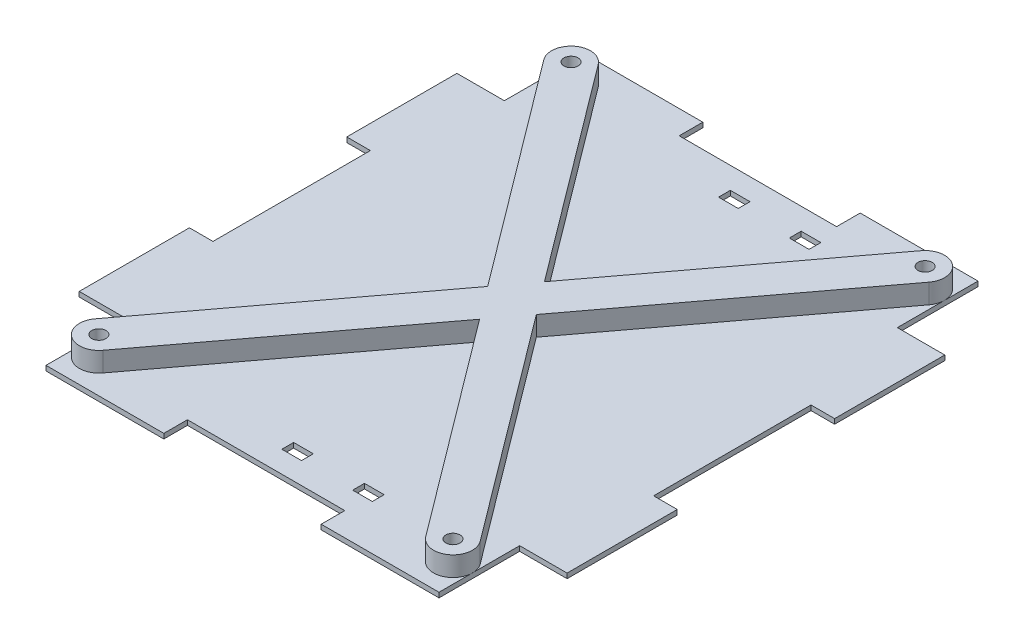
SolidWorks part; units mm, degrees
ref_plane "Front Plane" through (0, 0, 0) normal (0, 0, 1) x (1, 0, 0)
ref_plane "Top Plane" through (0, 0, 0) normal (0, 1, 0) x (1, 0, 0)
ref_plane "Right Plane" through (0, 0, 0) normal (1, 0, 0) x (0, 0, -1)
sketch "Sketch1" plane through (0, 0, 0) normal (0, 1, 0) x (1, 0, 0)
  line L0 (-25.4, 86.995) -> (-63.4314, 86.995)
  line L1 (-88.9, -101.6) -> (88.9, -101.6) construction
  line L2 (101.6, -88.9) -> (101.6, 88.9) construction
  line L3 (88.9, 101.6) -> (-88.9, 101.6) construction
  line L4 (-78.74, -60.96) -> (-63.4314, -60.96)
  line L5 (-63.4314, -60.96) -> (-63.4314, -86.995)
  line L6 (-63.4314, -86.995) -> (-25.4, -86.995)
  line L7 (63.4314, -86.995) -> (63.4314, -60.96)
  line L8 (63.4314, -60.96) -> (78.74, -60.96)
  line L9 (78.74, -60.96) -> (78.74, -25.4)
  line L10 (78.74, 60.96) -> (63.4314, 60.96)
  line L11 (63.4314, 60.96) -> (63.4314, 86.995)
  line L12 (63.4314, 86.995) -> (25.4, 86.995)
  line L13 (-63.4314, 86.995) -> (-63.4314, 60.96)
  line L14 (-63.4314, 60.96) -> (-78.74, 60.96)
  line L15 (-78.74, 60.96) -> (-78.74, 25.4)
  line L16 (-78.74, -25.4) -> (-78.74, -60.96)
  line L17 (-78.74, -25.4) -> (-71.12, -25.4)
  line L19 (-78.74, 25.4) -> (-71.12, 25.4)
  line L20 (-71.12, -25.4) -> (-71.12, 25.4)
  line L22 (-25.4, 86.995) -> (-25.4, 79.375)
  line L23 (-25.4, 79.375) -> (25.4, 79.375)
  line L24 (25.4, 86.995) -> (25.4, 79.375)
  line L25 (78.74, 25.4) -> (71.12, 25.4)
  line L27 (78.74, -25.4) -> (71.12, -25.4)
  line L28 (71.12, 25.4) -> (71.12, -25.4)
  line L30 (25.4, -86.995) -> (25.4, -79.375)
  line L31 (25.4, -79.375) -> (-25.4, -79.375)
  line L32 (-25.4, -86.995) -> (-25.4, -79.375)
  line L33 (78.74, 25.4) -> (78.74, 60.96)
  line L34 (25.4, -86.995) -> (63.4314, -86.995)
  line L35 (-101.6, 88.9) -> (-101.6, -88.9) construction
  arc A0 (88.9, -101.6) -> (101.6, -88.9) centre (88.9, -88.9) ccw construction
  arc A1 (-101.6, -88.9) -> (-88.9, -101.6) centre (-88.9, -88.9) ccw construction
  arc A2 (101.6, 88.9) -> (88.9, 101.6) centre (88.9, 88.9) ccw construction
  arc A3 (-101.6, 88.9) -> (-88.9, 101.6) centre (-88.9, 88.9) cw construction
  circle A4 centre (-57.15, 76.2) radius 2.286
  circle A5 centre (57.15, 76.2) radius 2.286
  circle A6 centre (57.15, -76.2) radius 2.286
  circle A7 centre (-57.15, -76.2) radius 2.286
  point P3 (0, 101.6)
  point P5 (101.6, 0)
  point P13 (101.6, 101.6)
  point P16 (-101.6, 101.6)
  point P38 (-71.12, 0)
  point P55 (0, -79.375)
  point P56 (0, 79.375)
  point P57 (71.12, 0)
  dimension "D2" = 12.7
  dimension "D11" = 4.572
  dimension "D8" = 44.45
  dimension "D1" = 203.2
  dimension "D3" = 203.2
  dimension "D4" = 22.86
  dimension "D5" = 15.3086
  dimension "D6" = 35.56
  dimension "D7" = 173.99
  dimension "D12" = 50.8
  dimension "D13" = 25.4
  dimension "D14" = 44.45
  dimension "D15" = 25.4
  dimension "D18" = 7.62
extrude "Main Body" add sketch "Sketch1" along normal blind 1.5875
sketch "Sketch2" plane through (0, 1.5875, 0) normal (0, 1, 0) x (1, 0, 0)
  line L0 (0, 0) -> (15.1112, 0) construction
  line L1 (-50.8, -63.5) -> (50.8, -63.5)
  line L2 (-50.8, -63.5) -> (-50.8, 63.5)
  line L3 (-50.8, 63.5) -> (50.8, 63.5)
  line L4 (50.8, -63.5) -> (50.8, 63.5)
  line L5 (-50.8, -63.5) -> (50.8, 63.5) construction
  line L6 (-50.8, 63.5) -> (50.8, -63.5) construction
  line L7 (-5.08, 63.5) -> (30.48, 63.5)
  line L8 (-5.08, 63.5) -> (-5.08, 68.58)
  line L9 (-5.08, 68.58) -> (30.48, 68.58)
  line L10 (30.48, 63.5) -> (30.48, 68.58)
  line L11 (-5.08, -63.5) -> (30.48, -63.5)
  line L12 (-5.08, -63.5) -> (-5.08, -68.58)
  line L13 (-5.08, -68.58) -> (30.48, -68.58)
  line L14 (30.48, -63.5) -> (30.48, -68.58)
  line L15 (-5.08, 68.58) -> (30.48, 68.58)
  line L16 (-5.08, 68.58) -> (-5.08, 72.39)
  line L17 (-5.08, 72.39) -> (30.48, 72.39)
  line L18 (30.48, 68.58) -> (30.48, 72.39)
  line L19 (-5.08, -68.58) -> (30.48, -68.58)
  line L20 (-5.08, -68.58) -> (-5.08, -72.39)
  line L21 (-5.08, -72.39) -> (30.48, -72.39)
  line L22 (30.48, -68.58) -> (30.48, -72.39)
  line L23 (-1.905, 68.58) -> (4.445, 68.58)
  line L24 (-1.905, 68.58) -> (-1.905, 72.39)
  line L25 (-1.905, 72.39) -> (4.445, 72.39)
  line L26 (4.445, 68.58) -> (4.445, 72.39)
  line L27 (20.955, 72.39) -> (27.305, 72.39)
  line L28 (-78.74, -25.4) -> (-78.74, -60.96)
  line L29 (-78.74, -60.96) -> (-63.4314, -60.96)
  line L30 (-63.4314, -60.96) -> (-63.4314, -86.995)
  line L31 (-63.4314, -86.995) -> (-25.4, -86.995)
  line L32 (-25.4, -86.995) -> (-25.4, -79.375)
  line L33 (-25.4, -79.375) -> (25.4, -79.375)
  line L34 (25.4, -79.375) -> (25.4, -86.995)
  line L35 (25.4, -86.995) -> (63.4314, -86.995)
  line L36 (63.4314, -86.995) -> (63.4314, -60.96)
  line L37 (63.4314, -60.96) -> (78.74, -60.96)
  line L38 (78.74, -60.96) -> (78.74, -25.4)
  line L39 (78.74, -25.4) -> (71.12, -25.4)
  line L40 (71.12, -25.4) -> (71.12, 25.4)
  line L41 (71.12, 25.4) -> (78.74, 25.4)
  line L42 (78.74, 25.4) -> (78.74, 60.96)
  line L43 (78.74, 60.96) -> (63.4314, 60.96)
  line L44 (63.4314, 60.96) -> (63.4314, 86.995)
  line L45 (63.4314, 86.995) -> (25.4, 86.995)
  line L46 (25.4, 86.995) -> (25.4, 79.375)
  line L47 (25.4, 79.375) -> (-25.4, 79.375)
  line L48 (-25.4, 79.375) -> (-25.4, 86.995)
  line L49 (-25.4, 86.995) -> (-63.4314, 86.995)
  line L50 (-63.4314, 86.995) -> (-63.4314, 60.96)
  line L51 (-63.4314, 60.96) -> (-78.74, 60.96)
  line L52 (-78.74, 60.96) -> (-78.74, 25.4)
  line L53 (-78.74, 25.4) -> (-71.12, 25.4)
  line L54 (-71.12, 25.4) -> (-71.12, -25.4)
  line L55 (-71.12, -25.4) -> (-78.74, -25.4)
  line L56 (-78.74, -25.4) -> (-78.74, -60.96)
  line L57 (-78.74, -60.96) -> (-63.4314, -60.96)
  line L58 (-63.4314, -60.96) -> (-63.4314, -86.995)
  line L59 (-63.4314, -86.995) -> (-25.4, -86.995)
  line L60 (-25.4, -86.995) -> (-25.4, -79.375)
  line L61 (-25.4, -79.375) -> (25.4, -79.375)
  line L62 (25.4, -79.375) -> (25.4, -86.995)
  line L63 (25.4, -86.995) -> (63.4314, -86.995)
  line L64 (63.4314, -86.995) -> (63.4314, -60.96)
  line L65 (63.4314, -60.96) -> (78.74, -60.96)
  line L66 (78.74, -60.96) -> (78.74, -25.4)
  line L67 (78.74, -25.4) -> (71.12, -25.4)
  line L68 (71.12, -25.4) -> (71.12, 25.4)
  line L69 (71.12, 25.4) -> (78.74, 25.4)
  line L70 (78.74, 25.4) -> (78.74, 60.96)
  line L71 (78.74, 60.96) -> (63.4314, 60.96)
  line L72 (63.4314, 60.96) -> (63.4314, 86.995)
  line L73 (63.4314, 86.995) -> (25.4, 86.995)
  line L74 (25.4, 86.995) -> (25.4, 79.375)
  line L75 (25.4, 79.375) -> (-25.4, 79.375)
  line L76 (-25.4, 79.375) -> (-25.4, 86.995)
  line L77 (-25.4, 86.995) -> (-63.4314, 86.995)
  line L78 (-63.4314, 86.995) -> (-63.4314, 60.96)
  line L79 (-63.4314, 60.96) -> (-78.74, 60.96)
  line L80 (-78.74, 60.96) -> (-78.74, 25.4)
  line L81 (-78.74, 25.4) -> (-71.12, 25.4)
  line L82 (-71.12, 25.4) -> (-71.12, -25.4)
  line L83 (-71.12, -25.4) -> (-78.74, -25.4)
  line L84 (20.955, 72.39) -> (20.955, 68.58)
  line L85 (20.955, 68.58) -> (27.305, 68.58)
  line L86 (27.305, 72.39) -> (27.305, 68.58)
  line L87 (20.955, -68.58) -> (27.305, -68.58)
  line L88 (27.305, -72.39) -> (27.305, -68.58)
  line L89 (20.955, -72.39) -> (27.305, -72.39)
  line L90 (20.955, -72.39) -> (20.955, -68.58)
  line L91 (-1.905, -72.39) -> (4.445, -72.39)
  line L92 (4.445, -68.58) -> (4.445, -72.39)
  line L93 (-1.905, -68.58) -> (4.445, -68.58)
  line L94 (-1.905, -68.58) -> (-1.905, -72.39)
  point P2 (0, 0)
  dimension "D2" = 101.6
  dimension "D3" = 127
  dimension "D4" = 35.56
  dimension "D5" = 20.32
  dimension "D6" = 5.08
  dimension "D7" = 3.81
  dimension "D8" = 6.35
  dimension "D9" = 6.35
  dimension "D10" = 3.175
  dimension "D11" = 3.175
  dimension "D1" = 0
extrude "Cut-Extrude1" cut sketch "Sketch2" against normal up to next contours L19 L94 L21 L92 | L90 L21 L88 L19 | L15 L26 L17 L24 | L86 L17 L84 L15 region at (1.27, 1.5875, 70.485) region at (24.13, 1.5875, 70.485) region at (1.27, 1.5875, -70.485) region at (24.13, 1.5875, -70.485)
sketch "Sketch3" plane through (0, 1.5875, 0) normal (0, 1, 0) x (1, 0, 0)
  line L0 (-57.15, -76.2) -> (57.15, 76.2) construction
  line L1 (52.1249, -79.9689) -> (62.1751, -72.4311)
  line L2 (-62.1751, 72.4311) -> (-52.1249, 79.9689)
  line L3 (62.1751, 72.4311) -> (52.1249, 79.9689)
  line L4 (-52.1249, -79.9689) -> (-62.1751, -72.4311)
  line L5 (-57.15, 76.2) -> (57.15, -76.2) construction
  line L6 (52.1249, 79.9689) -> (-62.1751, -72.4311)
  line L7 (-52.1249, -79.9689) -> (62.1751, 72.4311)
  line L8 (-52.1249, 79.9689) -> (62.1751, -72.4311)
  line L9 (52.1249, -79.9689) -> (-62.1751, 72.4311)
  line L28 (-78.74, -25.4) -> (-78.74, -60.96)
  line L29 (-78.74, -60.96) -> (-63.4314, -60.96)
  line L30 (-63.4314, -60.96) -> (-63.4314, -86.995)
  line L31 (-63.4314, -86.995) -> (-25.4, -86.995)
  line L32 (-25.4, -86.995) -> (-25.4, -79.375)
  line L33 (-25.4, -79.375) -> (25.4, -79.375)
  line L34 (25.4, -79.375) -> (25.4, -86.995)
  line L35 (25.4, -86.995) -> (63.4314, -86.995)
  line L36 (63.4314, -86.995) -> (63.4314, -60.96)
  line L37 (63.4314, -60.96) -> (78.74, -60.96)
  line L38 (78.74, -60.96) -> (78.74, -25.4)
  line L39 (78.74, -25.4) -> (71.12, -25.4)
  line L40 (71.12, -25.4) -> (71.12, 25.4)
  line L41 (71.12, 25.4) -> (78.74, 25.4)
  line L42 (78.74, 25.4) -> (78.74, 60.96)
  line L43 (78.74, 60.96) -> (63.4314, 60.96)
  line L44 (63.4314, 60.96) -> (63.4314, 86.995)
  line L45 (63.4314, 86.995) -> (25.4, 86.995)
  line L46 (25.4, 86.995) -> (25.4, 79.375)
  line L47 (25.4, 79.375) -> (-25.4, 79.375)
  line L48 (-25.4, 79.375) -> (-25.4, 86.995)
  line L49 (-25.4, 86.995) -> (-63.4314, 86.995)
  line L50 (-63.4314, 86.995) -> (-63.4314, 60.96)
  line L51 (-63.4314, 60.96) -> (-78.74, 60.96)
  line L52 (-78.74, 60.96) -> (-78.74, 25.4)
  line L53 (-78.74, 25.4) -> (-71.12, 25.4)
  line L54 (-71.12, 25.4) -> (-71.12, -25.4)
  line L55 (-71.12, -25.4) -> (-78.74, -25.4)
  line L56 (-78.74, -25.4) -> (-78.74, -60.96)
  line L57 (-78.74, -60.96) -> (-63.4314, -60.96)
  line L58 (-63.4314, -60.96) -> (-63.4314, -86.995)
  line L59 (-63.4314, -86.995) -> (-25.4, -86.995)
  line L60 (-25.4, -86.995) -> (-25.4, -79.375)
  line L61 (-25.4, -79.375) -> (25.4, -79.375)
  line L62 (25.4, -79.375) -> (25.4, -86.995)
  line L63 (25.4, -86.995) -> (63.4314, -86.995)
  line L64 (63.4314, -86.995) -> (63.4314, -60.96)
  line L65 (63.4314, -60.96) -> (78.74, -60.96)
  line L66 (78.74, -60.96) -> (78.74, -25.4)
  line L67 (78.74, -25.4) -> (71.12, -25.4)
  line L68 (71.12, -25.4) -> (71.12, 25.4)
  line L69 (71.12, 25.4) -> (78.74, 25.4)
  line L70 (78.74, 25.4) -> (78.74, 60.96)
  line L71 (78.74, 60.96) -> (63.4314, 60.96)
  line L72 (63.4314, 60.96) -> (63.4314, 86.995)
  line L73 (63.4314, 86.995) -> (25.4, 86.995)
  line L74 (25.4, 86.995) -> (25.4, 79.375)
  line L75 (25.4, 79.375) -> (-25.4, 79.375)
  line L76 (-25.4, 79.375) -> (-25.4, 86.995)
  line L77 (-25.4, 86.995) -> (-63.4314, 86.995)
  line L78 (-63.4314, 86.995) -> (-63.4314, 60.96)
  line L79 (-63.4314, 60.96) -> (-78.74, 60.96)
  line L80 (-78.74, 60.96) -> (-78.74, 25.4)
  line L81 (-78.74, 25.4) -> (-71.12, 25.4)
  line L82 (-71.12, 25.4) -> (-71.12, -25.4)
  line L83 (-71.12, -25.4) -> (-78.74, -25.4)
  circle A0 centre (-57.15, -76.2) radius 2.286 construction
  circle A1 centre (57.15, -76.2) radius 2.286 construction
  circle A2 centre (57.15, 76.2) radius 2.286 construction
  circle A3 centre (-57.15, 76.2) radius 2.286 construction
  circle A4 centre (-57.15, -76.2) radius 2.286
  circle A5 centre (57.15, -76.2) radius 2.286
  circle A6 centre (57.15, 76.2) radius 2.286
  circle A7 centre (-57.15, 76.2) radius 2.286
  circle A8 centre (-57.15, 76.2) radius 6.2814
  circle A9 centre (57.15, 76.2) radius 6.2814
  circle A10 centre (-57.15, -76.2) radius 6.2814
  circle A11 centre (57.15, -76.2) radius 6.2814
  point P42 (-57.15, 76.2)
  point P48 (57.15, 76.2)
  point P54 (-57.15, -76.2)
  point P56 (57.15, -76.2)
  circle M44 centre (57.15, -76.2) radius 2.286
  circle M45 centre (-57.15, 76.2) radius 2.286
  circle M74 centre (57.15, 76.2) radius 2.286
  circle M75 centre (-57.15, -76.2) radius 2.286
  dimension "D2" = 90
  dimension "D3" = 90
  dimension "D4" = 90
  dimension "D5" = 90
  dimension "D1" = 0
extrude "Boss-Extrude1" add sketch "Sketch3" along normal blind 6.35 contours A8 L9 L6 L8 | A9 L6 L8 L7 | L9 L7 L8 L6 | A10 L7 L9 L6 | A11 L8 L7 L9 | L2 A8 M45 | L2 A8 M45 | L3 A9 M74 | L3 A9 M74 | L1 A11 M44 | A11 L1 M44 | L4 A10 M75 | L4 A10 M75 region at (55.3951, 1.5875, 73.8602) region at (29.0976, 1.5875, 38.7205) region at (58.9049, 1.5875, 78.5398) region at (0, 1.5875, 0) region at (-29.0976, 1.5875, 38.7205) region at (-58.9049, 1.5875, 78.5398) region at (-55.3951, 1.5875, 73.8602) region at (29.0976, 1.5875, -38.7205) region at (-29.0976, 1.5875, -38.7205) region at (55.3951, 1.5875, -73.8602) region at (58.9049, 1.5875, -78.5398) region at (-58.9049, 1.5875, -78.5398) region at (-55.3951, 1.5875, -73.8602)
